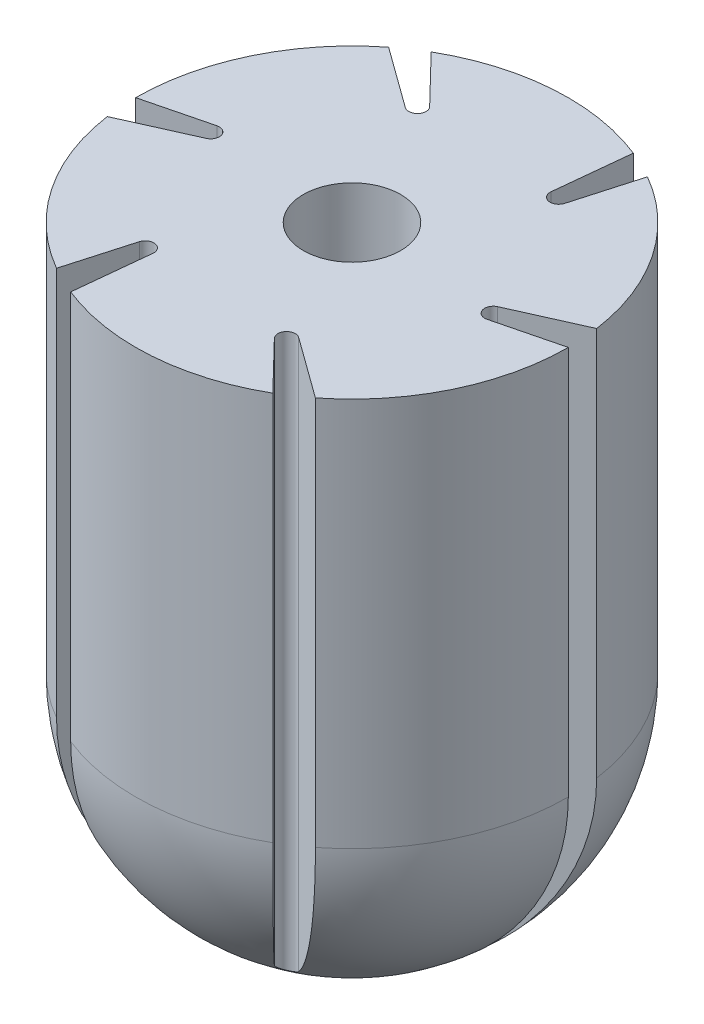
SolidWorks part; units mm, degrees
material "BUTYL"
ref_plane "Front Plane" through (0, 0, 0) normal (0, 0, 1) x (1, 0, 0)
ref_plane "Top Plane" through (0, 0, 0) normal (0, 1, 0) x (1, 0, 0)
ref_plane "Right Plane" through (0, 0, 0) normal (1, 0, 0) x (0, 0, -1)
sketch "Sketch1" plane through (0, 0, 0) normal (0, 0, 1) x (1, 0, 0)
  line L0 (0, 0) -> (0, 23823.6397) construction
  line L1 (0, 0) -> (23823.6397, 0) construction
  line L2 (-5, 9) -> (-1.125, 9)
  line L3 (-5, 9) -> (-5, 0)
  line L4 (-1.125, 9) -> (-1.125, 4)
  line L5 (-1.125, 4) -> (0, 4)
  line L6 (0, 4) -> (0, -5)
  arc A0 (-5, 0) -> (0, -5) centre (0, 0) ccw
  dimension "D1" = 5
  dimension "D2" = 1.125
  dimension "D3" = 14
  dimension "D4" = 5
revolve "Revolve1" add sketch "Sketch1" angle 360 about L0
sketch "Sketch2" plane through (0, 9, 0) normal (0, 1, 0) x (1, 0, 0)
  line L0 (-4.9498, -0.7068) -> (-3.3682, 0)
  line L1 (-5, 0) -> (-3.4984, 0.3766)
  circle A0 centre (0, 0) radius 5 construction
  arc A1 (-3.3682, 0) -> (-3.4984, 0.3766) centre (-3.4498, 0.1826) ccw
  arc A2 (-5, 0) -> (-4.9498, -0.7068) centre (0, 0) ccw
  dimension "D2" = 0.2
  dimension "D1" = 1.5
  dimension "D3" = 10
extrude "Cut-Extrude1" cut sketch "Sketch2" against normal through all
ref_axis "Axis1" through (0, 9.7, 0) along (0, -1, 0)
pattern_circular "CirPattern1" count 6 over 360 about axis through (0, 9, 0) along (0, -1, 0) of "Cut-Extrude1"
